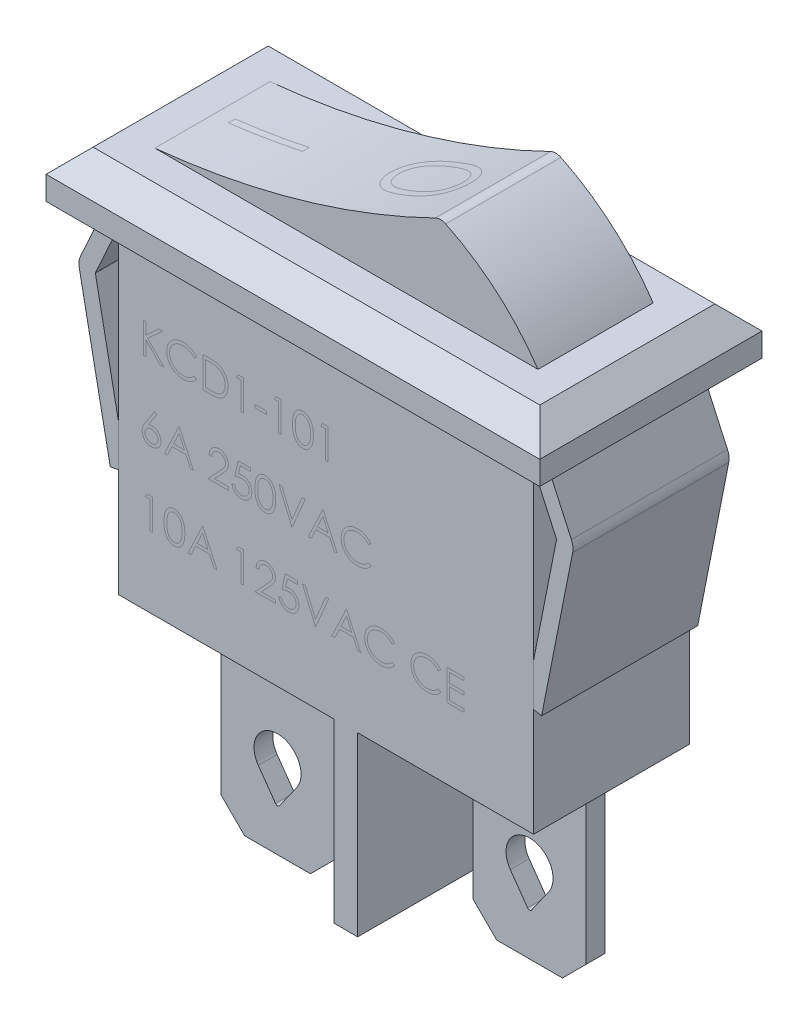
SolidWorks part; units mm, degrees
ref_plane "Front Plane" through (0, 0, 0) normal (0, 0, 1) x (1, 0, 0)
ref_plane "Top Plane" through (0, 0, 0) normal (0, 1, 0) x (1, 0, 0)
ref_plane "Right Plane" through (0, 0, 0) normal (1, 0, 0) x (0, 0, -1)
sketch "Sketch1" plane through (0, 0, 0) normal (0, 0, 1) x (1, 0, 0)
  line L1 (8.83, 7.175) -> (-8.83, 7.175)
  line L2 (8.83, 7.175) -> (8.83, -7.175)
  line L3 (8.83, -7.175) -> (-8.83, -7.175)
  line L4 (-8.83, 7.175) -> (-8.83, -7.175)
  line L5 (8.83, 7.175) -> (-8.83, -7.175) construction
  line L6 (8.83, -7.175) -> (-8.83, 7.175) construction
  point P0 (0, 0)
  dimension "D1" = 14.35
  dimension "D2" = 17.66
extrude "Boss-Extrude1" add sketch "Sketch1" along normal mid plane 6.64
sketch "Sketch2" plane through (0, 7.175, 0) normal (0, 1, 0) x (1, 0, 0)
  line L1 (10.5, 4.725) -> (-10.5, 4.725)
  line L2 (10.5, 4.725) -> (10.5, -4.725)
  line L3 (10.5, -4.725) -> (-10.5, -4.725)
  line L4 (-10.5, 4.725) -> (-10.5, -4.725)
  line L5 (10.5, 4.725) -> (-10.5, -4.725) construction
  line L6 (10.5, -4.725) -> (-10.5, 4.725) construction
  point P0 (0, 0)
  dimension "D1" = 9.45
  dimension "D2" = 21
extrude "Boss-Extrude2" add sketch "Sketch2" along normal blind 2
chamfer "Chamfer1" distance 1 angle 45 4 edges at (0, 9.175, -4.725) (10.5, 9.175, 0) (0, 9.175, 4.725) (-10.5, 9.175, 0)
sketch "Sketch3" plane through (0, 0, 0) normal (0, 0, 1) x (1, 0, 0)
  line L0 (8.15, 9.175) -> (4, 12.675) construction
  line L1 (-9.5, 9.175) -> (9.5, 9.175) construction
  line L2 (10.5, 8.175) -> (10.5, 7.175) construction
  line L4 (-10.5, 8.175) -> (-10.5, 7.175) construction
  line L5 (-8.15, 9.175) -> (8.15, 9.175)
  arc A0 (-8.15, 9.175) -> (3.7859, 12.5693) centre (-11.604, 44.0042) ccw
  arc A1 (4.2234, 12.5703) -> (8.15, 9.175) centre (-0.13, 3.5677) cw
  arc A2 (3.7859, 12.5693) -> (4.2234, 12.5703) centre (4.0058, 12.1202) cw
  point P6 (-8.15, 9.175)
  dimension "D4" = 35
  dimension "D5" = 6.5
  dimension "D6" = 10
  dimension "D7" = 0.5
  dimension "D1" = 2.35
  dimension "D2" = 3.5
  dimension "D3" = 2.35
extrude "Boss-Extrude3" add sketch "Sketch3" along normal mid plane 4.9
ref_plane "Plane1" through (0.35, 0, 0) normal (1, 0, 0) x (0, 0, -1)
sketch "Sketch4" plane through (0.35, 0, 0) normal (1, 0, 0) x (0, 0, -1)
  line L1 (-3.32, -7.175) -> (3.32, -7.175)
  line L2 (-3.32, -7.175) -> (-3.32, -14.695)
  line L3 (-3.32, -14.695) -> (3.32, -14.695)
  line L4 (3.32, -7.175) -> (3.32, -14.695)
  dimension "D1" = 7.52
extrude "Boss-Extrude4" add sketch "Sketch4" along normal blind 1
sketch "Sketch5" plane through (0, -7.175, 0) normal (0, -1, 0) x (1, 0, 0)
  line L0 (1.35, 3.32) -> (8.83, 3.32) construction
  line L1 (2.58, -0.36) -> (7.38, -0.36)
  line L2 (2.58, -0.36) -> (2.58, -1.16)
  line L3 (2.58, -1.16) -> (7.38, -1.16)
  line L4 (7.38, -0.36) -> (7.38, -1.16)
  line L5 (2.58, -0.36) -> (7.38, -1.16) construction
  line L6 (2.58, -1.16) -> (7.38, -0.36) construction
  line L7 (-6.62, 1.16) -> (-1.82, 1.16)
  line L8 (-6.62, 1.16) -> (-6.62, 0.36)
  line L9 (-6.62, 0.36) -> (-1.82, 0.36)
  line L10 (-1.82, 1.16) -> (-1.82, 0.36)
  line L11 (-6.62, 1.16) -> (-1.82, 0.36) construction
  line L12 (-6.62, 0.36) -> (-1.82, 1.16) construction
  line L13 (-8.83, -3.32) -> (0.35, -3.32) construction
  line L14 (8.83, 3.32) -> (8.83, -3.32) construction
  point P0 (4.98, -0.76)
  point P5 (-4.22, 0.76)
  dimension "D1" = 4.8
  dimension "D2" = 0.8
  dimension "D3" = 14
  dimension "D4" = 3.68
  dimension "D5" = 3.68
  dimension "D6" = 1.45
extrude "Boss-Extrude5" add sketch "Sketch5" along normal blind 8.36
chamfer "Chamfer2" distance 1 angle 45 4 edges at (7.38, -15.535, -0.76) (2.58, -15.535, -0.76) (-1.82, -15.535, 0.76) (-6.62, -15.535, 0.76)
sketch "Sketch6" plane through (0, 0, -0.36) normal (0, 0, 1) x (1, 0, 0)
  line L0 (6.38, -15.535) -> (3.58, -15.535) construction
  line L1 (4.8983, -13.6927) -> (4.1632, -12.6519)
  line L2 (4.98, -12.075) -> (4.98, -15.535) construction
  line L3 (-1.82, -10.855) -> (2.58, -10.855) construction
  line L4 (5.0617, -13.6927) -> (5.7968, -12.6519)
  line L5 (-1.82, -14.535) -> (-1.82, -7.175) construction
  line L6 (2.58, -14.535) -> (2.58, -7.175) construction
  line L7 (0.38, -10.855) -> (0.38, -14.695) construction
  line L8 (1.35, -14.695) -> (0.35, -14.695) construction
  line L9 (-4.3017, -13.6927) -> (-5.0368, -12.6519)
  line L10 (-4.1383, -13.6927) -> (-3.4032, -12.6519)
  arc A0 (5.7968, -12.6519) -> (4.1632, -12.6519) centre (4.98, -12.075) ccw
  arc A1 (5.0617, -13.6927) -> (4.8983, -13.6927) centre (4.98, -13.635) cw
  arc A2 (-4.3017, -13.6927) -> (-4.1383, -13.6927) centre (-4.22, -13.635) ccw
  arc A3 (-5.0368, -12.6519) -> (-3.4032, -12.6519) centre (-4.22, -12.075) cw
  dimension "D1" = 0.1
  dimension "D2" = 2.66
  dimension "D3" = 1
  dimension "D4" = 1.8
extrude "Cut-Extrude1" cut sketch "Sketch6" against normal through all and the other way through all
ref_plane "Plane2" through (-3.0237, 10.6328, 0) normal (0.2735, -0.9619, 0) x (-0.9619, -0.2735, 0)
sketch "Sketch7" plane through (-3.0237, 10.6328, 0) normal (0.2735, -0.9619, 0) x (-0.9619, -0.2735, 0)
  text T0 "<r90>I</r>" font "Century Gothic" height 3.2
  text T1 "<r90>0</r>"
wrap "Wrap1" sketch "Sketch7" wrap type scribe source sketch "Sketch7" face at (-2.1062, 10.6055, 0)
sketch "Sketch8" plane through (0, 0, 3.32) normal (0, 0, 1) x (1, 0, 0)
  text T0 "KCD1-101\r\n6A 250VAC\r\n10A 125VAC CE" font "Century Gothic" height 1.3
wrap "Wrap2" sketch "Sketch8" wrap type scribe source sketch "Sketch8" face at (-0.6162, -4.5275, 3.32)
sketch "Sketch9" plane through (0, 0, 0) normal (0, 0, 1) x (1, 0, 0)
  line L0 (-8.83, 7.175) -> (-10.175, 4.225)
  line L1 (-10.175, 4.225) -> (-8.83, -2.575)
  line L2 (-8.83, 7.175) -> (-8.83, -7.175) construction
  line L3 (8.83, 7.175) -> (10.175, 4.225)
  line L4 (10.175, 4.225) -> (8.83, -2.575)
  line L5 (8.83, -7.175) -> (8.83, 7.175) construction
  line L6 (-10.5, 7.175) -> (10.5, 7.175) construction
  dimension "D1" = 2.95
  dimension "D2" = 6.8
  dimension "D3" = 20.35
extrude "Extrude-Thin14" add sketch "Sketch9" against normal mid plane 6.64 separate body thin thin type mid plane wall 0.7
sketch "Sketch10" plane through (0, 0, 3.32) normal (0, 0, 1) x (1, 0, 0)
  line L2 (-8.83, -7.175) -> (8.83, -7.175)
  line L3 (-8.83, -7.175) -> (-8.83, 7.175)
  line L4 (-8.83, 7.175) -> (8.83, 7.175)
  line L5 (8.83, -7.175) -> (8.83, 7.175)
extrude "Cut-Extrude5" cut sketch "Sketch10" against normal through all
